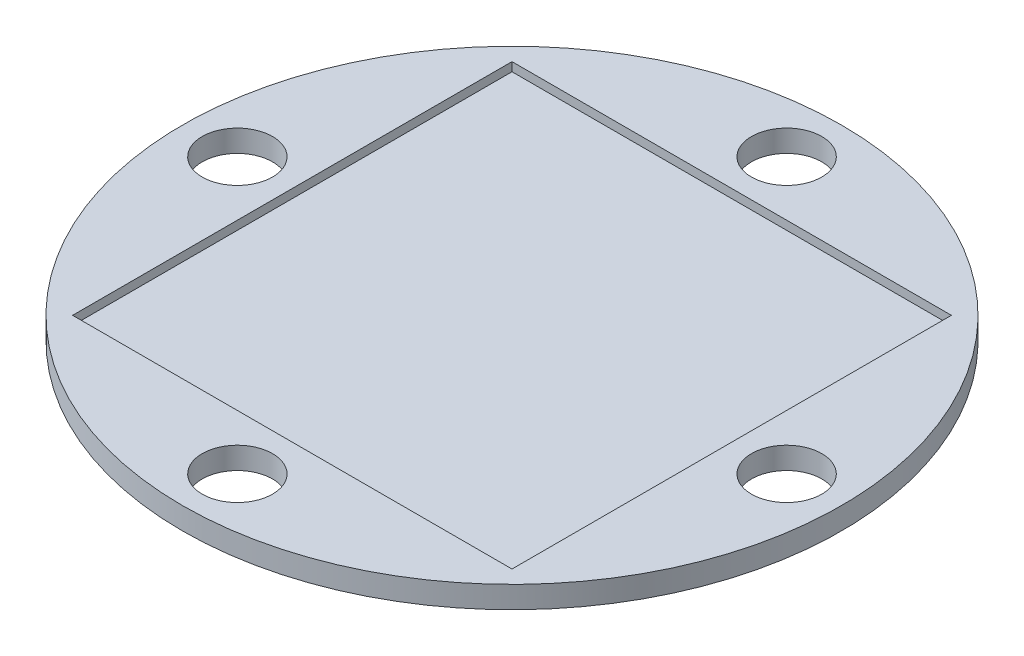
SolidWorks part; units mm, degrees
material "Custom Plastic"
ref_plane "Front Plane" through (0, 0, 0) normal (0, 0, 1) x (1, 0, 0)
ref_plane "Top Plane" through (0, 0, 0) normal (0, 1, 0) x (1, 0, 0)
ref_plane "Right Plane" through (0, 0, 0) normal (1, 0, 0) x (0, 0, -1)
sketch "Sketch1" plane through (0, 0, 0) normal (0, 1, 0) x (1, 0, 0)
  line L0 (0, 0) -> (0, -17.9724) construction
  line L1 (-50, -50) -> (50, -50)
  line L2 (-50, -50) -> (-50, 50)
  line L3 (-50, 50) -> (50, 50)
  line L4 (50, -50) -> (50, 50)
  line L5 (-50, -50) -> (50, 50) construction
  line L6 (-50, 50) -> (50, -50) construction
  line L7 (0, 0) -> (14.9739, 0) construction
  line L8 (0, 62.5) -> (14.3316, 62.5) construction
  line L9 (0, 75) -> (25.822, 75) construction
  circle A0 centre (0, 0) radius 75
  circle A1 centre (0, 0) radius 62.5 construction
  circle A2 centre (0, 62.5) radius 5
  circle A3 centre (62.5, 0) radius 5
  circle A4 centre (0, -62.5) radius 5
  circle A5 centre (-62.5, 0) radius 5
  dimension "D1" = 150
  dimension "D4" = 125
  dimension "D5" = 10
  dimension "D2" = 100
  dimension "D3" = 100
extrude "Boss-Extrude1" add sketch "Sketch1" along normal blind 5 contours L2 L1 L4 L3 | A0
sketch "Sketch3" plane through (0, 5, 0) normal (0, 1, 0) x (1, 0, 0)
  line L1 (-50, -50) -> (50, -50)
  line L2 (-50, -50) -> (-50, 50)
  line L3 (-50, 50) -> (50, 50)
  line L4 (50, -50) -> (50, 50)
  line L5 (-50, -50) -> (50, 50) construction
  line L6 (-50, 50) -> (50, -50) construction
  point P0 (0, 0)
extrude "Boss-Extrude2" add sketch "Sketch3" against normal blind 5
extrude "Cut-Extrude1" cut sketch "Sketch3<2>" against normal blind 2
sketch "Sketch3<2>" plane through (0, 5, 0) normal (0, 1, 0) x (1, 0, 0) same geometry as "Sketch3"
sketch "Sketch6" plane through (0, 5, 0) normal (0, 1, 0) x (1, 0, 0)
  circle A0 centre (0, 0) radius 62.5 construction
  circle A1 centre (0, 62.5) radius 8
  circle A2 centre (62.5, 0) radius 8
  circle A3 centre (0, -62.5) radius 8
  circle A4 centre (-62.5, 0) radius 8
  dimension "D1" = 125
  dimension "D2" = 16
extrude "Cut-Extrude2" cut sketch "Sketch6" against normal blind 10
